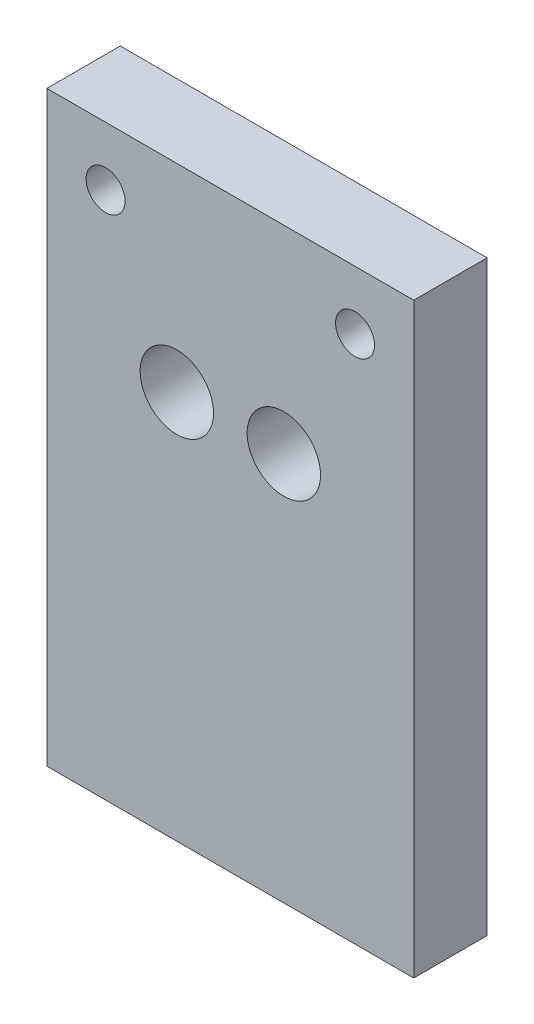
SolidWorks part; units mm, degrees
material "Acrylic (Medium-high impact)"
ref_plane "Front Plane" through (0, 0, 0) normal (0, 0, 1) x (1, 0, 0)
ref_plane "Top Plane" through (0, 0, 0) normal (0, 1, 0) x (1, 0, 0)
ref_plane "Right Plane" through (0, 0, 0) normal (1, 0, 0) x (0, 0, -1)
sketch "Sketch1" plane through (0, 0, 0) normal (0, 0, 1) x (1, 0, 0)
  line L1 (-31.75, 67.31) -> (31.75, 67.31)
  line L2 (-31.75, 67.31) -> (-31.75, -67.31)
  line L3 (-31.75, -67.31) -> (31.75, -67.31)
  line L4 (31.75, 67.31) -> (31.75, -67.31)
  line L5 (-31.75, 67.31) -> (31.75, -67.31) construction
  line L6 (-31.75, -67.31) -> (31.75, 67.31) construction
  circle A0 centre (-9.2608, 0) radius 6.35
  circle A1 centre (9.2608, 0) radius 6.35
  point P0 (0, 0)
  dimension "D3" = 12.7
  dimension "D4" = 12.7
  dimension "D1" = 63.5
  dimension "D2" = 134.62
  dimension "D5" = 9.2608
  dimension "D6" = 9.2608
extrude "Boss-Extrude1" add sketch "Sketch1" along normal blind 12.7
sketch "Sketch2" plane through (0, 0, 12.7) normal (0, 0, 1) x (1, 0, 0)
  line L0 (31.75, -67.31) -> (31.75, 67.31) construction
  line L1 (-31.75, 67.31) -> (31.75, 67.31)
  line L2 (-31.75, 67.31) -> (-31.75, 34.29)
  line L3 (-31.75, 34.29) -> (31.75, 34.29)
  line L4 (31.75, 67.31) -> (31.75, 34.29)
  dimension "D1" = 33.02
extrude "Cut-Extrude1" cut sketch "Sketch2" against normal through all
sketch "Sketch3" plane through (0, 0, 12.7) normal (0, 0, 1) x (1, 0, 0)
  line L0 (-9.2608, 0) -> (-9.2608, -83.7414) construction
hole_wizard "1/4 Clearance Hole1" positions "Sketch6" profile "Sketch5" hole size "1/4" standard "ANSI Inch" end condition through all
sketch "Sketch6" plane through (0, 0, 12.7) normal (0, 0, 1) x (1, 0, 0)
  line L0 (-31.75, 34.29) -> (31.75, 34.29) construction
  line L1 (-31.75, 34.29) -> (-31.75, -67.31) construction
  point P0 (-21.59, 24.13)
  dimension "D1" = 10.16
  dimension "D2" = 10.16
sketch "Sketch5" plane through (-21.59, 24.13, 12.7) normal (1, 0, 0) x (0, -1, 0)
  line L0 (0, 0) -> (0, 12.7)
  line L1 (0, 12.7) -> (3.3782, 12.7)
  line L2 (3.3782, 12.7) -> (3.3782, 0)
  line L5 (3.3782, 0) -> (0, 0)
  line L11 (0, -6.35) -> (0, 107.95) construction
  dimension "Thru Hole Dia." = 6.7564
  dimension "Thru Hole Depth" = 12.7
mirror "Mirror1" about plane through (0, 0, 0) normal (1, 0, 0) of "1/4 Clearance Hole1"
